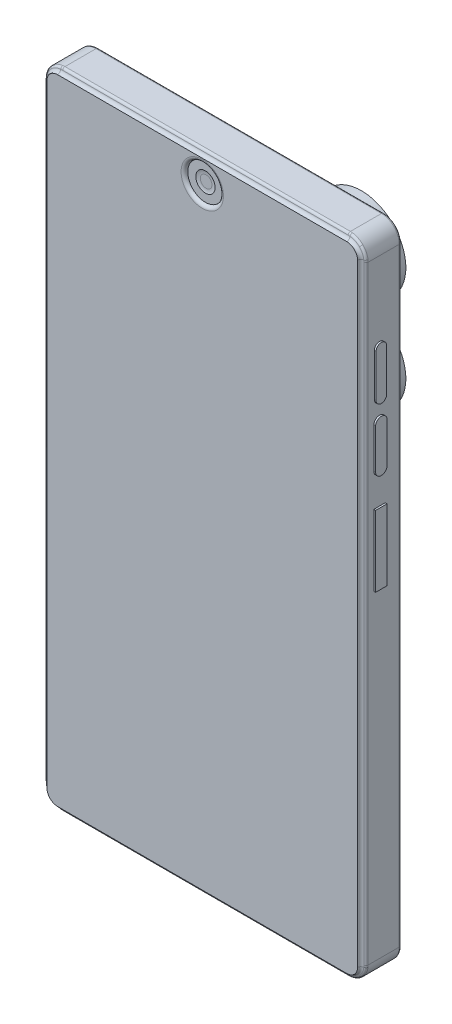
SolidWorks part; units mm, degrees
ref_plane "Front Plane" through (0, 0, 0) normal (0, 0, 1) x (1, 0, 0)
ref_plane "Top Plane" through (0, 0, 0) normal (0, 1, 0) x (1, 0, 0)
ref_plane "Right Plane" through (0, 0, 0) normal (1, 0, 0) x (0, 0, -1)
sketch "Sketch1" plane through (0, 0, 0) normal (0, 0, 1) x (1, 0, 0)
  line L1 (-45.1187, 90.5423) -> (45.1187, 90.5423)
  line L2 (-45.1187, 90.5423) -> (-45.1187, -90.5423)
  line L3 (-45.1187, -90.5423) -> (45.1187, -90.5423)
  line L4 (45.1187, 90.5423) -> (45.1187, -90.5423)
  line L5 (-45.1187, 90.5423) -> (45.1187, -90.5423) construction
  line L6 (-45.1187, -90.5423) -> (45.1187, 90.5423) construction
  point P0 (0, 0)
extrude "Boss-Extrude1" add sketch "Sketch1" along normal blind 10
fillet "Fillet1" radius 5 4 edges at (45.1187, -90.5423, 5) (-45.1187, -90.5423, 5) (-45.1187, 90.5423, 5) (45.1187, 90.5423, 5)
sketch "Sketch2" plane through (0, 0, 0) normal (0, 0, -1) x (-1, 0, 0)
  line L0 (-29.8312, 76.1407) -> (-29.8312, 22.7286) construction
  line L1 (-16.7623, 76.1407) -> (-16.7623, 22.7286)
  line L2 (-42.9002, 76.1407) -> (-42.9002, 22.7286)
  arc A0 (-16.7623, 76.1407) -> (-42.9002, 76.1407) centre (-29.8312, 76.1407) ccw
  arc A1 (-42.9002, 22.7286) -> (-16.7623, 22.7286) centre (-29.8312, 22.7286) ccw
  circle A2 centre (-8.114, 73.9954) radius 6.9733
  point P2 (-29.8312, 49.4346)
extrude "Cut-Extrude3" cut sketch "Sketch2" against normal blind 1 contours L2 A1 L1 A0
sketch "Sketch3" plane through (0, 0, 0) normal (0, 0, -1) x (-1, 0, 0)
  line L0 (-29.8312, 89.2096) -> (-29.8312, 63.4191) construction
  line L1 (-29.8312, 61.6505) -> (-29.8312, 9.6596) construction
  line L2 (-16.7623, 22.7286) -> (-42.9002, 22.7286) construction
  line L5 (-42.9002, 76.1407) -> (-16.7623, 76.1407) construction
  line L6 (-16.7623, 76.1407) -> (-17.3362, 75.7868) construction
  line L7 (-29.8312, 10.007) -> (-29.8312, 9.6596) construction
  line L8 (-42.3262, 75.7868) -> (-42.9002, 76.1407) construction
  circle A0 centre (-9.6596, 75.2883) radius 5
  arc A1 (-16.7623, 76.1407) -> (-42.9002, 76.1407) centre (-29.8312, 76.1407) ccw construction
  arc A2 (-42.9002, 22.7286) -> (-16.7623, 22.7286) centre (-29.8312, 22.7286) ccw construction
  circle A3 centre (-29.8312, 76.1407) radius 12.5
  circle A5 centre (-29.8312, 49.1505) radius 12.5
  circle A6 centre (-29.8312, 22.7286) radius 8.568
  dimension "D1" = 25
  dimension "D2" = 25
extrude "Boss-Extrude2" add sketch "Sketch3" along normal blind 4 contours A0 | A3 | A5 | A6
sketch "Sketch4" plane through (0, 0, -4) normal (0, 0, -1) x (-1, 0, 0)
  line L0 (-9.6596, 80.2883) -> (-9.6596, 70.2883) construction
  circle A0 centre (-9.6596, 75.2883) radius 5 construction
  circle A1 centre (-9.6596, 75.2883) radius 2.9002
extrude "Cut-Extrude4" cut sketch "Sketch4" against normal blind 1
sketch "Sketch5" plane through (0, 0, -4) normal (0, 0, -1) x (-1, 0, 0)
  line L0 (-42.9002, 62.7201) -> (-16.7623, 62.7201) construction
  line L1 (-42.9002, 76.1407) -> (-42.9002, 22.7286) construction
  line L2 (-16.7623, 76.1407) -> (-16.7623, 22.7286) construction
  line L3 (-42.3312, 49.1505) -> (-17.3312, 49.1505) construction
  circle A0 centre (-29.8054, 76.0857) radius 12
  circle A1 centre (-29.8312, 49.1505) radius 12.5 construction
  circle A2 centre (-29.8312, 49.1505) radius 12
extrude "Cut-Extrude5" cut sketch "Sketch5" against normal blind 1
sketch "Sketch6" plane through (0, 0, -4) normal (0, 0, -1) x (-1, 0, 0)
  line L0 (-29.8312, 31.2966) -> (-29.8312, 31.0629) construction
  line L1 (-29.8312, 14.1605) -> (-30.0682, 14.3975) construction
  line L2 (-38.3993, 22.7286) -> (-35.913, 22.7286) construction
  line L3 (-21.4968, 22.7286) -> (-21.2632, 22.7286) construction
  line L4 (-29.8312, 16.6468) -> (-29.8312, 14.1605) construction
  line L5 (-33.7396, 18.0689) -> (-34.4909, 18.8202) construction
  line L6 (-38.1623, 22.4915) -> (-38.3993, 22.7286) construction
  circle A0 centre (-29.8312, 22.7286) radius 8.568 construction
  circle A1 centre (-29.8312, 22.7286) radius 8.568
  circle A2 centre (-29.8312, 22.7286) radius 6.0818
  circle A3 centre (-29.8312, 22.7286) radius 8.3344
  dimension "D1" = 17.1361
extrude "Cut-Extrude7" cut sketch "Sketch6" against normal blind 3 contours A3 A2 region at (37.9299, 22.7286, -4)
sketch "Sketch8" plane through (0, 0, 10) normal (0, 0, 1) x (1, 0, 0)
  line L1 (-43.6543, 89.0779) -> (43.6543, 89.0779)
  line L2 (-43.6543, 89.0779) -> (-43.6543, -89.0779)
  line L3 (-43.6543, -89.0779) -> (43.6543, -89.0779)
  line L4 (43.6543, 89.0779) -> (43.6543, -89.0779)
  arc A0 (40.1187, -90.5423) -> (45.1187, -85.5423) centre (40.1187, -85.5423) ccw construction
  arc A1 (-40.1187, 90.5423) -> (-45.1187, 85.5423) centre (-40.1187, 85.5423) ccw construction
extrude "Boss-Extrude3" add sketch "Sketch8" along normal blind 0.9
fillet "Fillet2" radius 3 4 edges at (-43.6543, 89.0779, 10.45) (-43.6543, -89.0779, 10.45) (43.6543, -89.0779, 10.45) (43.6543, 89.0779, 10.45)
sketch "Sketch9" plane through (0, 0, 10.9) normal (0, 0, 1) x (1, 0, 0)
  circle A0 centre (0, 82.8243) radius 4.9578
extrude "Cut-Extrude8" cut sketch "Sketch9" against normal blind 0.9
sketch "Sketch10" plane through (45.1187, 0, 0) normal (1, 0, 0) x (0, 0, -1)
  line L0 (-6.1744, 63.1826) -> (-6.1744, 51.2826) construction
  line L1 (-4.6912, 63.1826) -> (-4.6912, 51.2826)
  line L2 (-7.6575, 63.1826) -> (-7.6575, 51.2826)
  line L3 (-6.1744, 45.0803) -> (-6.1744, 33.8892) construction
  line L4 (-4.5564, 45.0803) -> (-4.5564, 33.8892)
  line L5 (-7.7923, 45.0803) -> (-7.7923, 33.8892)
  line L7 (-7.7923, 24.5858) -> (-4.5564, 24.5858)
  line L8 (-7.7923, 24.5858) -> (-7.7923, 4.6306)
  line L9 (-7.7923, 4.6306) -> (-4.5564, 4.6306)
  line L10 (-4.5564, 24.5858) -> (-4.5564, 4.6306)
  arc A0 (-4.6912, 63.1826) -> (-7.6575, 63.1826) centre (-6.1744, 63.1826) ccw
  arc A1 (-7.6575, 51.2826) -> (-4.6912, 51.2826) centre (-6.1744, 51.2826) ccw
  arc A2 (-4.5564, 45.0803) -> (-7.7923, 45.0803) centre (-6.1744, 45.0803) ccw
  arc A3 (-7.7923, 33.8892) -> (-4.5564, 33.8892) centre (-6.1744, 33.8892) ccw
  point P2 (-6.1744, 57.2326)
  point P7 (-6.1744, 39.4848)
  dimension "D1" = 11.9
  dimension "D2" = 11.1911
extrude "Boss-Extrude4" add sketch "Sketch10" along normal blind 0.5
sketch "Sketch11" plane through (-45.1187, 0, 0) normal (-1, 0, 0) x (0, 0, 1)
  line L0 (5, 77.7146) -> (5, 52.6007) construction
  line L1 (6.7967, 77.7146) -> (6.7967, 52.6007)
  line L2 (3.2033, 77.7146) -> (3.2033, 52.6007)
  arc A0 (6.7967, 77.7146) -> (3.2033, 77.7146) centre (5, 77.7146) ccw
  arc A1 (3.2033, 52.6007) -> (6.7967, 52.6007) centre (5, 52.6007) ccw
  point P2 (5, 65.1576)
extrude "Boss-Extrude5" add sketch "Sketch11" along normal blind 0.5
sketch "Sketch12" plane through (-45.6187, 0, 0) normal (-1, 0, 0) x (0, 0, 1)
  circle A0 centre (5.0445, 77.7883) radius 0.6377
extrude "Cut-Extrude9" cut sketch "Sketch12" against normal blind 6.5
sketch "Sketch13" plane through (0, -90.5423, 0) normal (0, -1, 0) x (1, 0, 0)
  line L0 (-7.9221, 5) -> (4.3901, 5) construction
  line L1 (-7.9221, 6.862) -> (4.3901, 6.862)
  line L2 (-7.9221, 3.138) -> (4.3901, 3.138)
  arc A0 (-7.9221, 6.862) -> (-7.9221, 3.138) centre (-7.9221, 5) ccw
  arc A1 (4.3901, 3.138) -> (4.3901, 6.862) centre (4.3901, 5) ccw
  circle A2 centre (20.8885, 5) radius 2.9899
  point P2 (-1.766, 5)
extrude "Cut-Extrude10" cut sketch "Sketch13" against normal blind 15.5
sketch "Sketch18" plane through (0, 0, 10) normal (0, 0, 1) x (1, 0, 0)
  circle A0 centre (0, 82.8243) radius 2.7164
extrude "Cut-Extrude12" cut sketch "Sketch18" against normal blind 0.2
fillet "Fillet4" radius 3 1 edges at (2.7164, 82.8243, 9.8)
fillet "Fillet5" radius 1 1 edges at (4.9578, 82.8243, 10.9)
fillet "Fillet6" radius 1 2 edges at (23.7495, 22.7286, -1) (23.7495, 22.7286, -4)
fillet "Fillet7" radius 1 2 edges at (21.2632, 22.7286, -4) (21.2632, 22.7286, 0)
fillet "Fillet8" radius 1 1 edges at (17.3312, 49.1505, 0)
fillet "Fillet9" radius 1 1 edges at (17.8054, 76.0857, -3)
fillet "Fillet10" radius 1 1 edges at (17.8312, 49.1505, -3)
fillet "Fillet11" radius 1 2 edges at (6.7595, 75.2883, -4) (14.6596, 75.2883, 0)
fillet "Fillet12" radius 1 4 edges at (29.8312, 89.2096, 1) (42.9002, 49.4346, 1) (29.8312, 9.6596, 1) (16.7623, 49.4346, 1)
fillet "Fillet13" radius 1 8 edges at (-42.7756, 88.1992, 10) (0, 89.0779, 10) (42.7756, 88.1992, 10) (43.6543, 0, 10) (42.7756, -88.1992, 10) (0, -89.0779, 10) (-42.7756, -88.1992, 10) (-43.6543, 0, 10)
fillet "Fillet15" radius 0.65 20 edges at (44.7381, -87.4558, 10) (42.0322, -90.1617, 10) (0, -90.5423, 10) (-42.0322, -90.1617, 10) (-44.7381, -87.4558, 10) (-45.1187, 0, 10) (-44.7381, 87.4558, 10) (-42.0322, 90.1617, 10) (0, 90.5423, 10) (42.0322, 90.1617, 10) (44.7381, 87.4558, 10) (43.6543, -89.0779, 0) (0, -90.5423, 0) (-43.6543, -89.0779, 0) (-45.1187, 0, 0) (-43.6543, 89.0779, 0) (0, 90.5423, 0) (43.6543, 89.0779, 0) (45.1187, 0, 10) (45.1187, 0, 0)
